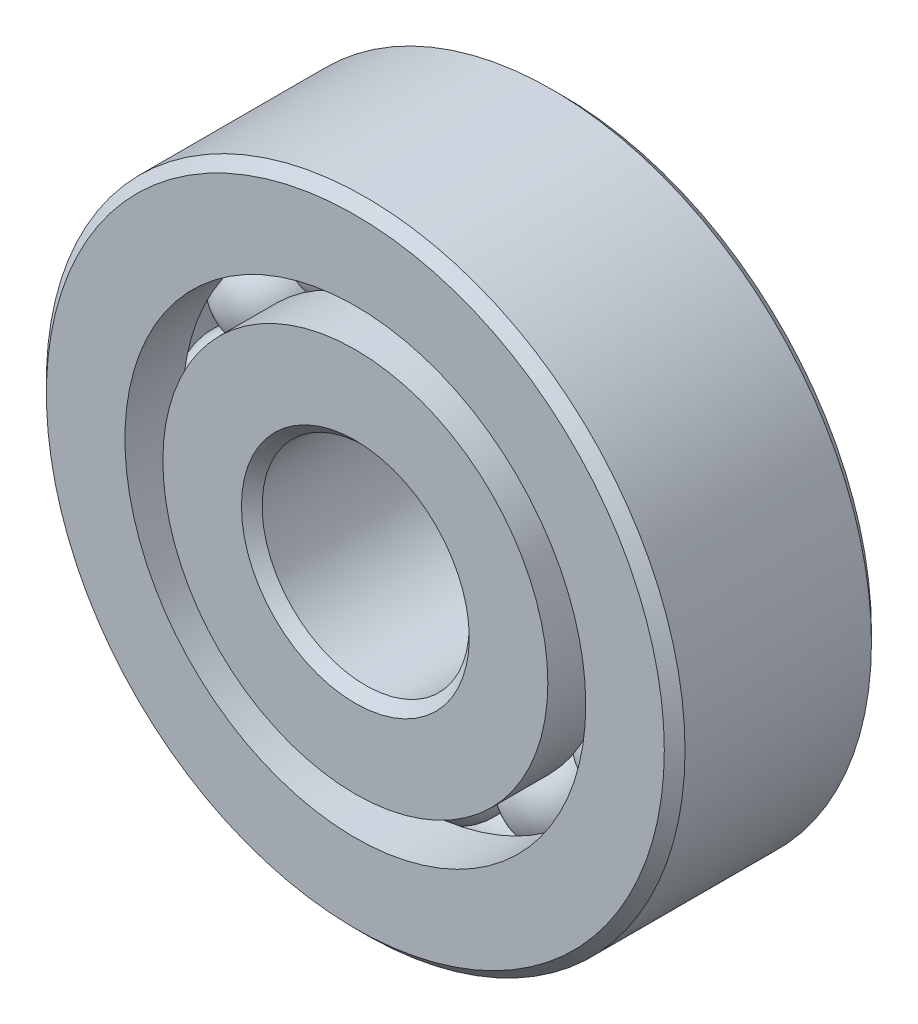
SolidWorks part; units mm, degrees
ref_plane "Front Plane" through (0, 0, 0) normal (0, 0, 1) x (1, 0, 0)
ref_plane "Top Plane" through (0, 0, 0) normal (0, 1, 0) x (1, 0, 0)
ref_plane "Right Plane" through (0, 0, 0) normal (1, 0, 0) x (0, 0, -1)
sketch "Sketch1" plane through (0, 0, 0) normal (1, 0, 0) x (0, 0, -1)
  line L0 (-6, 0) -> (6, 0) construction
  line L1 (0, 18.5) -> (0, -18.5) construction
  line L2 (5.4, 18.5) -> (-5.4, 18.5)
  line L3 (-5.4, 18.5) -> (-6, 17.9)
  line L4 (-6, 17.9) -> (-6, 13.3489)
  line L5 (-6, 13.3489) -> (-2.6667, 13.3489)
  line L6 (6, 13.3489) -> (2.6667, 13.3489)
  line L7 (6, 17.9) -> (6, 13.3489)
  line L8 (5.4, 18.5) -> (6, 17.9)
  line L9 (0, 18.5) -> (0, 12.25) construction
  line L10 (0, 12.25) -> (0, 6) construction
  arc A0 (-2.6667, 13.3489) -> (2.6667, 13.3489) centre (0, 12.25) cw
  point P14 (0, 6)
  dimension "D3" = 5.3333
  dimension "D1" = 45
  dimension "Width" = 12
  dimension "OD" = 37
  dimension "D2" = 0.6
  dimension "Shaft Dia" = 12
  dimension "D4" = 1.0989
revolve "Revolve1" add sketch "Sketch1" angle 360 about L0
sketch "Sketch3" plane through (0, 0, 0) normal (1, 0, 0) x (0, 0, -1)
  line L0 (-6, 11.1511) -> (-2.6667, 11.1511)
  line L1 (0, 18.5) -> (0, -18.5) construction
  line L2 (-6, 17.9) -> (-6, 13.3489) construction
  line L3 (-6, 11.1511) -> (-6, 6.6)
  line L4 (-5.4, 18.5) -> (-6, 17.9) construction
  line L5 (-6, 6.6) -> (-5.4, 6)
  line L6 (-5.4, 6) -> (5.4, 6)
  line L7 (5.4, 18.5) -> (5.4, -18.5) construction
  line L8 (5.4, 6) -> (6, 6.6)
  line L9 (6, -17.9) -> (6, 17.9) construction
  line L10 (6, 6.6) -> (6, 11.1511)
  line L11 (6, 11.1511) -> (2.6667, 11.1511)
  line L13 (5.4, 18.5) -> (6, 17.9) construction
  arc A0 (2.6667, 13.3489) -> (-2.6667, 13.3489) centre (0, 12.25) ccw construction
  arc A1 (2.6667, 11.1511) -> (-2.6667, 11.1511) centre (0, 12.25) cw
revolve "Revolve3" add sketch "Sketch3" angle 360 about L0
sketch "Sketch4" plane through (0, 0, 0) normal (1, 0, 0) x (0, 0, -1)
  line L0 (-2.8842, 12.25) -> (2.8842, 12.25)
  arc A2 (-2.8842, 12.25) -> (2.8842, 12.25) centre (0, 12.25) cw
  arc A3 (2.6667, 13.3489) -> (-2.6667, 13.3489) centre (0, 12.25) ccw construction
revolve "Revolve4" add sketch "Sketch4" angle 360 about L0
ref_axis "Axis1" through (0, 0, -6) along (0, 0, 1)
pattern_circular "CirPattern1" count 12 every 30 about axis through (0, 0, -6) along (0, 0, 1) of bodies 104
sketch "Sketch5" plane through (0, 0, 0) normal (1, 0, 0) x (0, 0, -1)
  line L0 (-6, 13.3489) -> (-2.6667, 13.3489) construction
  line L1 (-5.7, 13.3489) -> (-2.8842, 13.3489)
  line L2 (-5.7, 13.3489) -> (-5.7, 11.1511)
  line L3 (-5.7, 11.1511) -> (-2.8842, 11.1511)
  line L4 (-2.8842, 13.3489) -> (-2.8842, 11.1511)
  line L5 (-6, 11.1511) -> (-2.6667, 11.1511) construction
  line L6 (6, 13.3489) -> (2.6667, 13.3489) construction
  line L7 (5.7, 13.3489) -> (2.8842, 13.3489)
  line L8 (5.7, 13.3489) -> (5.7, 11.1511)
  line L9 (5.7, 11.1511) -> (2.8842, 11.1511)
  line L10 (2.8842, 13.3489) -> (2.8842, 11.1511)
  line L11 (6, 11.1511) -> (2.6667, 11.1511) construction
  line L12 (-5.4, 18.5) -> (-6, 17.9) construction
  point P18 (-5.7, 18.2)
equation "\"D2@Sketch1\" = \"Width@Sketch1\"*.05"
equation "\"D3@Sketch1\" = \"Width@Sketch1\"/2.25"
equation "\"D4@Sketch1\" = (((\"OD@Sketch1\"-\"Width@Sketch1\")/2)/3.25)/3.5"
equation "\"D2@CirPattern1\" = 360/\"Balls@CirPattern1\""
